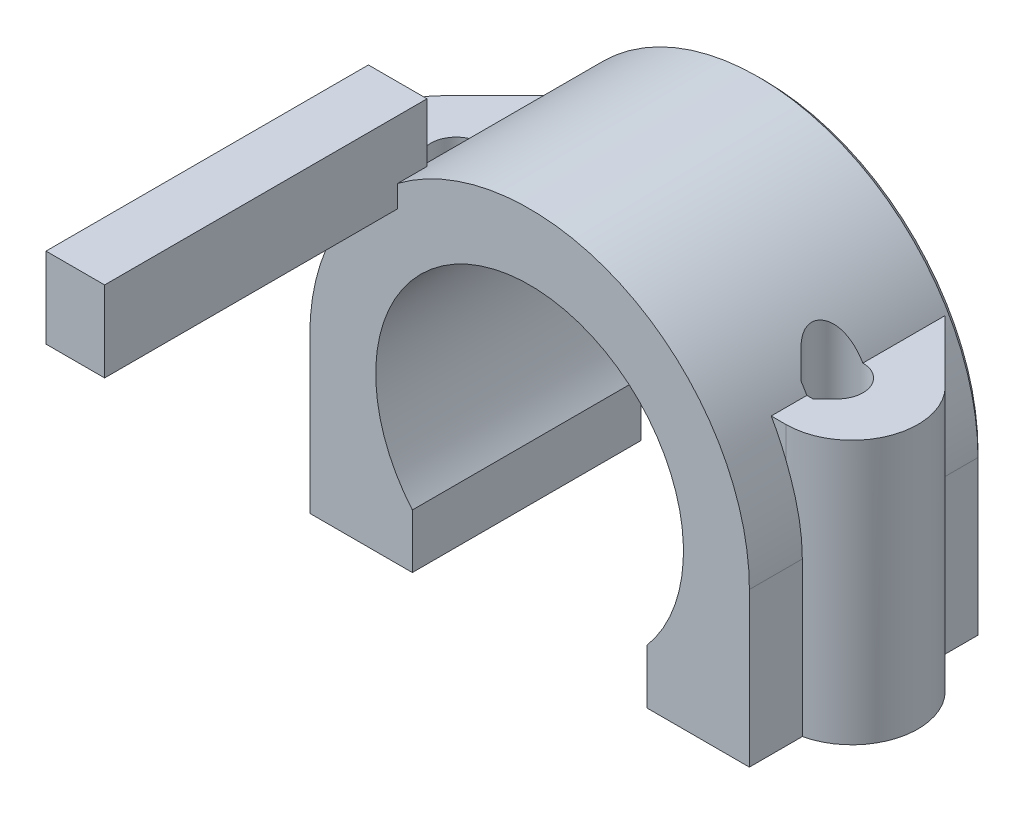
SolidWorks part; units mm, degrees
material "Custom Plastic"
ref_plane "Front Plane" through (0, 0, 0) normal (0, 0, 1) x (1, 0, 0)
ref_plane "Top Plane" through (0, 0, 0) normal (0, 1, 0) x (1, 0, 0)
ref_plane "Right Plane" through (0, 0, 0) normal (1, 0, 0) x (0, 0, -1)
sketch "Sketch1" plane through (0, 0, 0) normal (0, 0, 1) x (1, 0, 0)
  line L0 (-23.622, -10.5) -> (30.4823, -10.5) construction
  line L1 (-23.622, -16.5) -> (30.4823, -16.5) construction
  line L2 (8, -6.8007) -> (8, -10.5)
  line L3 (8, -10.5) -> (15, -10.5)
  line L4 (-15, -10.5) -> (-8, -10.5)
  line L5 (-8, -6.8007) -> (-8, -10.5)
  line L6 (15, 0) -> (15, -10.5)
  line L12 (-15, -10.5) -> (-15, 0)
  arc A4 (8, -6.8007) -> (-8, -6.8007) centre (0, 0) ccw
  arc A5 (15, 0) -> (-15, 0) centre (0, 0) ccw
  dimension "D1" = 16
  dimension "D6" = 21
  dimension "D7" = 4.5
  dimension "D2" = 6
extrude "Boss-Extrude1" add sketch "Sketch1" along normal blind 16
sketch "Sketch4" plane through (0, -10.5, 0) normal (0, -1, 0) x (1, 0, 0)
  line L0 (14, 8) -> (15, 8) construction
  line L1 (15, 16) -> (15, 0) construction
  line L2 (14, 12.5) -> (14, 3.5) construction
  line L3 (14, 12.5) -> (10.5, 12.5)
  line L4 (10.5, 0) -> (10.5, 16) construction
  line L5 (10.5, 12.5) -> (10.5, 3.5)
  line L6 (10.5, 3.5) -> (14, 3.5) construction
  line L7 (17.182, 4.818) -> (12.364, 0)
  line L8 (12.364, 0) -> (10.5, 0)
  line L9 (10.5, 0) -> (10.5, 3.5)
  arc A0 (17.182, 4.818) -> (14, 12.5) centre (14, 8) ccw
  dimension "D1" = 9
  dimension "D2" = 1
  dimension "D3" = 45
extrude "Boss-Extrude2" add sketch "Sketch4" against normal blind 18
sketch "Sketch2" plane through (0, -10.5, 0) normal (0, -1, 0) x (1, 0, 0)
  line L0 (13, 16) -> (13, 0) construction
  line L3 (14, 8) -> (13, 8) construction
  circle A0 centre (13, 8) radius 1.75
  arc A2 (17.182, 4.818) -> (15, 12.3875) centre (14, 8) ccw construction
  dimension "D1" = 3.5
  dimension "D2" = 1
extrude "Cut-Extrude1" cut sketch "Sketch2" against normal through all
mirror "Mirror1" about plane through (0, 0, 0) normal (1, 0, 0) of "Boss-Extrude2", "Cut-Extrude1"
chamfer "Chamfer1" distance 0.4 angle 45 8 edges at (-15, -5.25, 0) (-11.5, -10.5, 0) (-8, -8.6504, 0) (0, 10.5, 0) (8, -8.6504, 0) (11.5, -10.5, 0) (15, -5.25, 0) (0, 15, 0) tangent propagation no
sketch "Sketch5" plane through (0, -10.5, 0) normal (0, -1, 0) x (1, 0, 0)
  line L0 (-13, 8) -> (-11.7626, 9.2374)
  line L1 (-11.7626, 9.2374) -> (-12.5951, 10.07)
  line L2 (-12.5951, 10.07) -> (-13.4049, 10.07)
  line L3 (-13.4049, 10.07) -> (-14.2374, 9.2374)
  line L4 (-14.2374, 9.2374) -> (-13, 8)
  line L5 (13, 8) -> (14.2374, 9.2374)
  line L6 (14.2374, 9.2374) -> (13.4049, 10.07)
  line L7 (13.4049, 10.07) -> (12.5951, 10.07)
  line L8 (12.5951, 10.07) -> (11.7626, 9.2374)
  line L9 (11.7626, 9.2374) -> (13, 8)
  circle A0 centre (-13, 8) radius 1.75 construction
  circle A3 centre (13, 8) radius 1.75 construction
  point P0 (-13, 9.75)
  point P11 (13, 9.75)
  dimension "D1" = 0.32
  dimension "D2" = 0.32
extrude "Cut-Extrude3" cut sketch "Sketch5" against normal through all
sketch "Sketch6" plane through (0, 0, 16) normal (0, 0, -1) x (-1, 0, 0)
  line L0 (-18.5, -10.5) -> (-15, -10.5) construction
  line L2 (13, 10.5) -> (9, 10.5)
  line L3 (13, 10.5) -> (13, 16)
  line L4 (13, 16) -> (9, 16)
  line L5 (9, 10.5) -> (9, 16)
  line L6 (13, 10.5) -> (9, 16) construction
  line L7 (13, 16) -> (9, 10.5) construction
  point P0 (11, 13.25)
  point P4 (11, 13.25)
  dimension "D1" = 11
  dimension "D2" = 23.75
  dimension "D3" = 4
  dimension "D4" = 5.5
extrude "Boss-Extrude3" add sketch "Sketch6" against normal blind 20 and the other way blind 2
